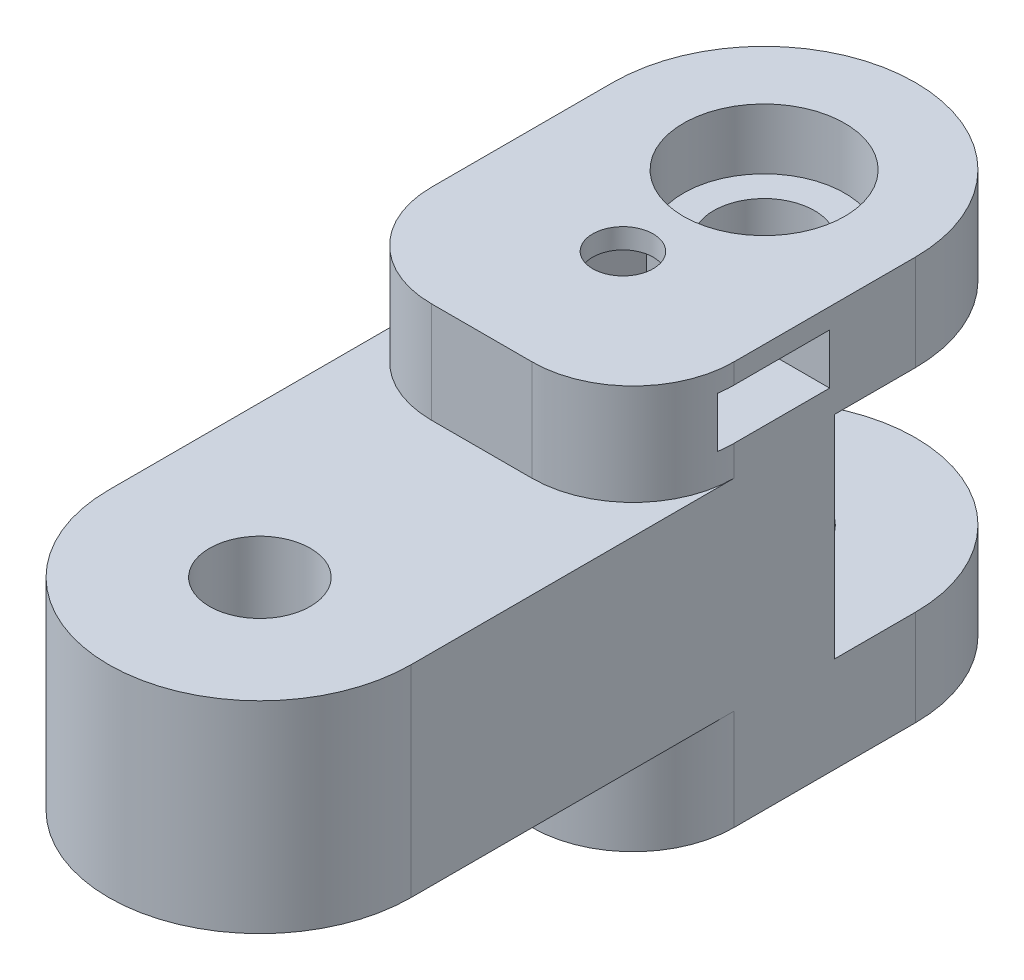
SolidWorks part; units mm, degrees
ref_plane "Front Plane" through (0, 0, 0) normal (0, 0, 1) x (1, 0, 0)
ref_plane "Top Plane" through (0, 0, 0) normal (0, 1, 0) x (1, 0, 0)
ref_plane "Right Plane" through (0, 0, 0) normal (1, 0, 0) x (0, 0, -1)
sketch "Sketch1" plane through (0, 0, 0) normal (0, 0, 1) x (1, 0, 0)
  line L1 (7.5, -10) -> (-7.5, -10)
  line L2 (7.5, -10) -> (7.5, 10)
  line L3 (7.5, 10) -> (-7.5, 10)
  line L4 (-7.5, -10) -> (-7.5, 10)
  line L5 (7.5, -10) -> (-7.5, 10) construction
  line L6 (7.5, 10) -> (-7.5, -10) construction
  point P0 (0, 0)
  dimension "D1" = 15
  dimension "D2" = 20
extrude "Boss-Extrude1" add sketch "Sketch1" along normal mid plane 40
sketch "Sketch2" plane through (0, -10, 0) normal (0, -1, 0) x (1, 0, 0)
  line L0 (-7.5, 20) -> (7.5, 20) construction
  point P3 (0, 0)
  point P4 (0, 20)
fillet "Fillet1" radius 7.5 2 edges at (-7.5, 0, -20) (7.5, 0, -20)
sketch "Sketch3" plane through (0, 10, 0) normal (0, 1, 0) x (1, 0, 0)
  circle A0 centre (0, 12.5) radius 8.5
  arc A1 (7.5, 12.5) -> (0, 20) centre (0, 12.5) ccw construction
  dimension "D1" = 1
extrude "Cut-Extrude1" cut sketch "Sketch3" against normal blind 10.5 from offset 4.75 offset against normal yes
sketch "Sketch4" plane through (0, 10, 0) normal (0, 1, 0) x (1, 0, 0)
  circle A0 centre (0, 12.5) radius 2.5
  dimension "D1" = 5
extrude "Cut-Extrude2" cut sketch "Sketch4" against normal through all
sketch "Sketch5" plane through (0, -10, 0) normal (0, -1, 0) x (-1, 0, 0)
  line L1 (-2.0207, 16) -> (-4.0415, 12.5)
  line L2 (-4.0415, 12.5) -> (-2.0207, 9)
  line L3 (-2.0207, 9) -> (2.0207, 9)
  line L4 (2.0207, 9) -> (4.0415, 12.5)
  line L5 (4.0415, 12.5) -> (2.0207, 16)
  line L6 (2.0207, 16) -> (-2.0207, 16)
  circle A0 centre (0, 12.5) radius 3.5 construction
  dimension "D1" = 7
extrude "Cut-Extrude3" cut sketch "Sketch5" against normal blind 3
sketch "Sketch6" plane through (0, 10, 0) normal (0, 1, 0) x (1, 0, 0)
  circle A0 centre (0, 12.5) radius 4
  dimension "D1" = 8
extrude "Cut-Extrude4" cut sketch "Sketch6" against normal blind 3
sketch "Sketch7" plane through (0, -10, 0) normal (0, -1, 0) x (1, 0, 0)
  line L0 (7.5, 20) -> (7.5, -12.5) construction
  line L1 (-7.5, 20) -> (-7.5, -12.5) construction
  line L2 (-7.5, 12.5) -> (7.5, 12.5) construction
  line L3 (-7.5, 12.5) -> (-7.5, 22.5)
  line L4 (-7.5, 22.5) -> (7.5, 22.5)
  line L5 (7.5, 22.5) -> (7.5, 12.5)
  arc A0 (7.5, 12.5) -> (-7.5, 12.5) centre (0, 12.5) ccw
  dimension "D1" = 10
extrude "Cut-Extrude5" cut sketch "Sketch7" against normal through all
sketch "Sketch8" plane through (0, -10, 0) normal (0, -1, 0) x (1, 0, 0)
  circle A0 centre (0, 12.5) radius 8.5
  arc A1 (7.5, 12.5) -> (-7.5, 12.5) centre (0, 12.5) ccw construction
  dimension "D1" = 1
extrude "Cut-Extrude6" cut sketch "Sketch8" against normal blind 5
ref_plane "Plane1" through (0, 0, 0) normal (0, 1, 0) x (1, 0, 0)
mirror "Mirror3" about plane through (0, 0, 0) normal (0, 1, 0) of "Cut-Extrude6"
sketch "Sketch9" plane through (0, -5, 0) normal (0, -1, 0) x (1, 0, 0)
  circle A0 centre (0, 12.5) radius 2.5
  dimension "D1" = 5
extrude "Cut-Extrude7" cut sketch "Sketch9" against normal through all
sketch "Sketch10" plane through (0, 10, 0) normal (0, 1, 0) x (1, 0, 0)
  line L0 (1.5877, 2.75) -> (7.5, 2.75)
  line L1 (-1.5877, 8.25) -> (-3.1754, 5.5)
  line L2 (-3.1754, 5.5) -> (-1.5877, 2.75)
  line L3 (-1.5877, 2.75) -> (1.5877, 2.75)
  line L4 (1.5877, 2.75) -> (3.1754, 5.5) construction
  line L5 (3.1754, 5.5) -> (1.5877, 8.25) construction
  line L6 (1.5877, 8.25) -> (-1.5877, 8.25)
  line L7 (7.5, -8.5) -> (7.5, 12.5) construction
  line L8 (7.5, 2.75) -> (7.5, 8.25)
  line L9 (7.5, 8.25) -> (1.5877, 8.25)
  circle A0 centre (0, 5.5) radius 2.75 construction
  point P1 (0, 12.5)
  dimension "D1" = 7
  dimension "D2" = 5.5
extrude "Cut-Extrude8" cut sketch "Sketch10" against normal blind 2.5 from offset 1 offset against normal yes
sketch "Sketch11" plane through (0, 10, 0) normal (0, 1, 0) x (1, 0, 0)
  circle A0 centre (0, 5.5) radius 1.5
  point P2 (0, 12.5)
  point P3 (0, 0)
  dimension "D2" = 3
  dimension "D1" = 7
extrude "Cut-Extrude9" cut sketch "Sketch11" against normal blind 10
sketch "Sketch12" plane through (0, 10, 0) normal (0, 1, 0) x (1, 0, 0)
  line L0 (-7.5, -8.5) -> (-7.5, 12.5) construction
  line L1 (-7.5, -1.5) -> (7.5, -1.5)
  line L2 (-7.5, -1.5) -> (-7.5, -8.5)
  line L3 (-7.5, -8.5) -> (7.5, -8.5)
  line L4 (7.5, -1.5) -> (7.5, -8.5)
  line L5 (-7.5, -1.5) -> (7.5, -8.5) construction
  line L6 (-7.5, -8.5) -> (7.5, -1.5) construction
  line L7 (7.5, -8.5) -> (7.5, 12.5) construction
  arc A0 (7.5, -8.5) -> (-7.5, -8.5) centre (0, -12.5) ccw construction
  point P0 (0, -5)
  point P10 (8.0829, -9.8701)
  dimension "D1" = 7
extrude "Cut-Extrude10" cut sketch "Sketch12" against normal up to surface (5 mm away) up to face at (0, 5, 15)
sketch "Sketch13" plane through (0, -10, 0) normal (0, -1, 0) x (1, 0, 0)
  line L0 (7.5, 8.5) -> (7.5, -12.5) construction
  line L1 (7.5, 1.5) -> (-7.5, 1.5)
  line L2 (7.5, 1.5) -> (7.5, 8.5)
  line L3 (7.5, 8.5) -> (-7.5, 8.5)
  line L4 (-7.5, 1.5) -> (-7.5, 8.5)
  line L5 (7.5, 1.5) -> (-7.5, 8.5) construction
  line L6 (7.5, 8.5) -> (-7.5, 1.5) construction
  point P0 (0, 5)
  dimension "D1" = 7
extrude "Cut-Extrude11" cut sketch "Sketch13" against normal up to surface (5 mm away) up to face at (0, -5, 10)
fillet "Fillet2" radius 5 4 edges at (-7.5, 7.5, 1.5) (7.5, 7.5, 1.5) (7.5, -7.5, 1.5) (-7.5, -7.5, 1.5)
